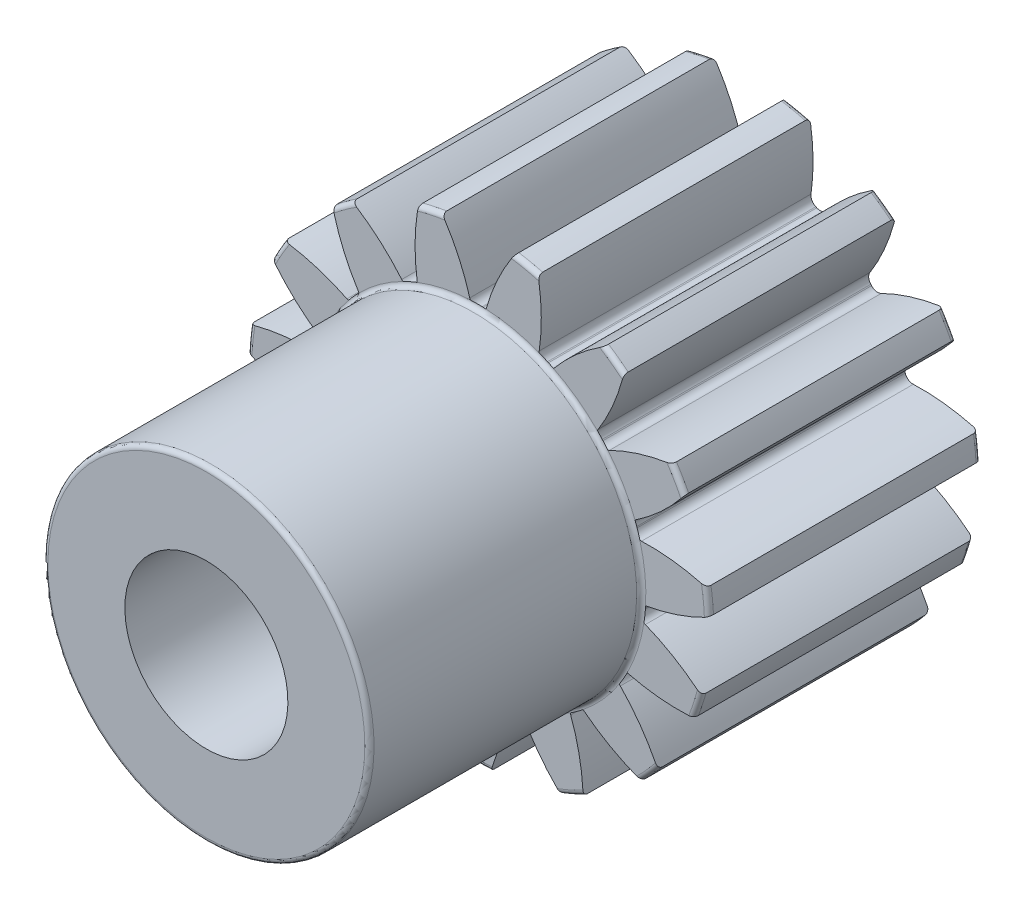
SolidWorks part; units mm, degrees
ref_plane "Front Plane" through (0, 0, 0) normal (0, 0, 1) x (1, 0, 0)
ref_plane "Top Plane" through (0, 0, 0) normal (0, 1, 0) x (1, 0, 0)
ref_plane "Right Plane" through (0, 0, 0) normal (1, 0, 0) x (0, 0, -1)
sketch "Sketch1" plane through (0, 0, 0) normal (0, 0, 1) x (1, 0, 0)
  line L0 (-190.5, 0) -> (190.5, 0) construction
  circle A0 centre (0, 0) radius 8.5 construction
  circle A1 centre (0, 0) radius 7.5 construction
  circle A2 centre (0, 0) radius 6 construction
  circle A3 centre (0, 0) radius 6 construction
  circle A4 centre (0, 0) radius 3 construction
  dimension "D2" = 1
  dimension "D3" = 2.5
  dimension "D1" = 2.5
sketch "Sketch2" plane through (0, 0, 0) normal (1, 0, 0) x (0, 0, -1)
  line L0 (0, 0) -> (-10, 0) construction
  line L1 (-10, 0) -> (-20, 0) construction
  dimension "Overall Width" = 20
  dimension "Face Width" = 10
sketch "Sketch4" plane through (0, 0, 0) normal (1, 0, 0) x (0, 0, -1)
  line L0 (-20, 3) -> (-20, 6)
  line L1 (-20, 6) -> (-10, 6)
  line L2 (-10, 6) -> (-10, 8.5)
  line L3 (-10, 8.5) -> (0, 8.5)
  line L4 (0, 8.5) -> (0, 3)
  line L5 (-10, 6) -> (-10, 0) construction
  line L6 (0, 8.5) -> (0, -8.5) construction
  line L7 (-10, 6) -> (0, 6) construction
  line L12 (-20, 3) -> (0, 3)
revolve "Revolve1" add sketch "Sketch4" angle 360 about L1
fillet "Fillet2" radius 0.17 4 edges at (0, 6, 20) (0, 6, 10) (0, 8.5, 10) (0, 8.5, 0)
sketch "Sketch7" plane through (0, 0, 10) normal (0, 0, 1) x (1, 0, 0)
  line L0 (0, 0) -> (0, 8.5) construction
  line L1 (0.784, 7.4589) -> (1.2469, 8.408) construction
  line L3 (1.7672, 8.3143) -> (1.5593, 7.3361) construction
  line L4 (1.5593, 7.3361) -> (1.2475, 5.8689) construction
  line L5 (0, 0) -> (1.2475, 5.8689) construction
  line L6 (0.784, 7.4589) -> (0, 0) construction
  line L7 (0.784, 7.4589) -> (0.8885, 8.4534) construction
  line L8 (0.784, 7.4589) -> (0, 0) construction
  circle A0 centre (0, 0) radius 8.5 construction
  arc A1 (-0.02, 6) -> (0.02, 6) centre (0, 0) cw
  circle A2 centre (0, 0) radius 6 construction
  arc A3 (-0.784, 7.4589) -> (0.784, 7.4589) centre (0, 0) cw construction
  circle A4 centre (0, 0) radius 7.5 construction
  arc A5 (2.2018, 8.2099) -> (1.3279, 8.3956) centre (0, 0) ccw construction
  arc A6 (0.784, 7.4589) -> (2.3176, 7.1329) centre (0, 0) cw construction
  arc A7 (-1.3279, 8.3956) -> (1.3279, 8.3956) centre (0, 0) cw
  arc A8 (0.3097, 6.2181) -> (1.3279, 8.3956) centre (7.5249, 4.1711) cw
  arc A9 (-0.3097, 6.2181) -> (-1.3279, 8.3956) centre (-7.5249, 4.1711) ccw
  arc A10 (-0.02, 6) -> (-0.3097, 6.2181) centre (-0.021, 6.3) cw
  arc A11 (0.02, 6) -> (0.3097, 6.2181) centre (0.021, 6.3) ccw
  point P26 (-0.25, 5.9948)
  point P29 (0.25, 5.9948)
  dimension "D4" = 0.3
  dimension "D5" = 7.5
  dimension "D3" = 20
  dimension "D1" = 3.1416
  dimension "D2" = 1.5708
extrude "Cut-Extrude2" cut sketch "Sketch7" against normal through all
pattern_circular "CirPattern1" count 15 over 360 about axis through (0, 0, 20) along (0, 0, -1) of "Cut-Extrude2"
equation "\"D1@Sketch1\"=2.5*(\"Pitch Dia.@Sketch1\"/\"Number of Teeth@Sketch1\")"
equation "\"D1@CirPattern1\"=\"Number of Teeth@Sketch1\""
equation "\"D1@Fillet2\"=\"OD@Sketch1\"*.01"
equation "\"D1@Sketch7\"=3.14159*(\"Pitch Dia.@Sketch1\"/\"Number of Teeth@Sketch1\")"
equation "\"D2@Sketch7\"=\"D1@Sketch7\"/2"
equation "\"D4@Sketch7\"=\"D1@Sketch7\"*.0955"
equation "\"D5@Sketch7\"=\"Pitch Dia.@Sketch1\"/2"
